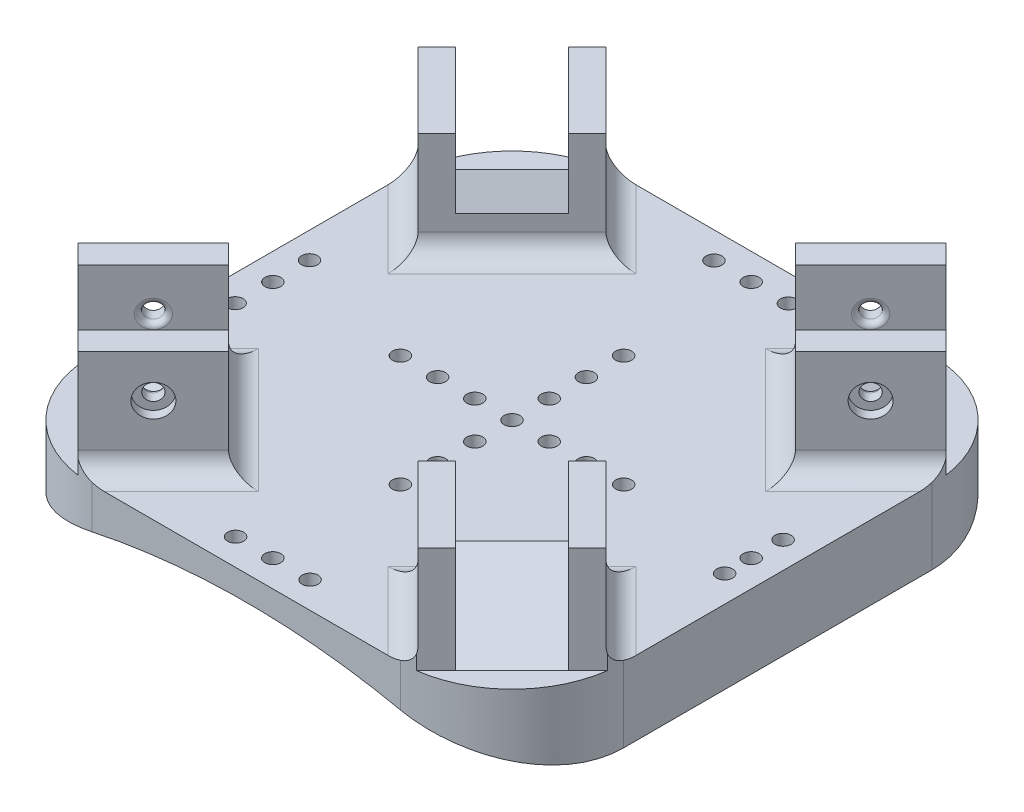
SolidWorks part; units mm, degrees
ref_plane "Front Plane" through (0, 0, 0) normal (0, 0, 1) x (1, 0, 0)
ref_plane "Top Plane" through (0, 0, 0) normal (0, 1, 0) x (1, 0, 0)
ref_plane "Right Plane" through (0, 0, 0) normal (1, 0, 0) x (0, 0, -1)
sketch "Sketch1" plane through (0, 0, 0) normal (0, 0, 1) x (1, 0, 0)
  line L0 (0, 0) -> (50, 0) construction
  line L1 (0, 0) -> (-50, 0) construction
  line L2 (-50, 0) -> (-50, 5) construction
  line L3 (50, 0) -> (50, 5) construction
  line L4 (50, 5) -> (-50, 5) construction
  line L5 (-50, 5) -> (-50, 0)
  line L6 (50, 5) -> (50, 0)
  arc A0 (-50, 0) -> (50, 0) centre (0, -130.767) cw
  arc A1 (50, 5) -> (-50, 5) centre (0, -130.767) ccw
  dimension "D1" = 50
  dimension "D2" = 50
extrude "Boss-Extrude1" add sketch "Sketch1" along normal blind 100
sketch "Sketch2" plane through (0, 0, 100) normal (0, 0, 1) x (1, 0, 0)
  line L0 (0, 13.9143) -> (50, 13.9143) construction
  line L1 (50, 13.9143) -> (50, 5) construction
  line L2 (0, 13.9143) -> (-50, 13.9143) construction
  line L3 (-50, 13.9143) -> (-50, 5) construction
  line L4 (-50, 5) -> (-50, 13.9143)
  line L5 (-50, 13.9143) -> (0, 13.9143)
  line L6 (0, 13.9143) -> (50, 13.9143)
  line L7 (50, 13.9143) -> (50, 5)
  line L8 (50, 5) -> (0, 13.9143)
  line L9 (0, 13.9143) -> (-50, 5)
  arc A0 (50, 5) -> (-50, 5) centre (0, -130.767) ccw construction
  arc M3 (50, 5) -> (-50, 5) centre (0, -130.767) ccw
extrude "Boss-Extrude2" add sketch "Sketch2" against normal blind 100 contours L5 L4 M3 | L7 L6 M3 region at (37.5783, 11.2548, 100) region at (-37.5783, 11.2548, 100)
sketch "Sketch3" plane through (0, 13.9143, 0) normal (0, 1, 0) x (1, 0, 0)
  line L0 (-50, 0) -> (50, -100) construction
  line L1 (50, 0) -> (-50, -100) construction
  circle A0 centre (0, -50) radius 1.5
extrude "Cut-Extrude1" cut sketch "Sketch3" against normal blind 10
sketch "Sketch4" plane through (0, 13.9143, 0) normal (0, 1, 0) x (1, 0, 0)
  line L0 (-50, 0) -> (50, -100) construction
  line L1 (50, 0) -> (-50, -100) construction
  line L2 (31.9688, -0.3536) -> (17.8266, -14.4957)
  line L3 (31.9688, -0.3536) -> (49.6464, -18.0312)
  line L4 (17.8266, -14.4957) -> (35.5043, -32.1734)
  line L5 (49.6464, -18.0312) -> (35.5043, -32.1734)
  line L6 (31.9688, -0.3536) -> (35.5043, -32.1734) construction
  line L7 (17.8266, -14.4957) -> (49.6464, -18.0312) construction
  point P9 (33.7365, -16.2635)
  dimension "D1" = 20
  dimension "D2" = 25
  dimension "D3" = 23
  dimension "D4" = 0
  dimension "D5" = 0
extrude "Boss-Extrude3" add sketch "Sketch4" along normal blind 20
sketch "Sketch5" plane through (33.8388, 0, 33.8388) normal (0.7071, 0, 0.7071) x (0.7071, 0, -0.7071)
  line L0 (2.3553, 20.9143) -> (22.3553, 13.9143)
  line L1 (22.3553, 33.9143) -> (22.3553, 13.9143) construction
  line L2 (2.3553, 33.9143) -> (22.3553, 33.9143)
  line L3 (2.3553, 33.9143) -> (2.3553, 20.9143)
  line L4 (2.3553, 20.9143) -> (22.3553, 20.9143)
  line L5 (22.3553, 33.9143) -> (22.3553, 20.9143)
  line L6 (22.3553, 13.9143) -> (22.3553, 20.9143)
  line M3 (22.3553, 13.9143) -> (22.3553, 33.9143)
  line M4 (22.3553, 33.9143) -> (2.3553, 33.9143)
  line M5 (2.3553, 33.9143) -> (2.3553, 13.9143)
  dimension "D1" = 13
sketch "Sketch6" plane through (33.8388, 0, 33.8388) normal (0.7071, 0, 0.7071) x (0.7071, 0, -0.7071)
  line L0 (2.3553, 33.9143) -> (22.3553, 33.9143) construction
  line L1 (22.3553, 33.9143) -> (22.3553, 13.9143) construction
  circle A0 centre (12.3553, 25.9143) radius 1.55
  dimension "D1" = 8
  dimension "D2" = 10
extrude "Cut-Extrude3" cut sketch "Sketch6" against normal blind 25
extrude "Cut-Extrude4" cut sketch "Sketch5" against normal blind 15 from offset 5 contours L4 M5 M3 M4 | L4 L0 M3 region at (44.9324, 18.581, 22.7453) region at (42.5754, 27.4143, 25.1023) offset against normal yes
sketch "Sketch7" plane through (33.8388, 0, 33.8388) normal (0.7071, 0, 0.7071) x (0.7071, 0, -0.7071)
  circle A0 centre (12.3553, 25.9143) radius 3
extrude "Cut-Extrude5" cut sketch "Sketch7" against normal blind 2
extrude "Cut-Extrude6" cut sketch "Sketch7<2>" along normal blind 2 from offset 25 offset against normal yes
sketch "Sketch7<2>" plane through (33.8388, 0, 33.8388) normal (0.7071, 0, 0.7071) x (0.7071, 0, -0.7071) same geometry as "Sketch7"
fillet "Fillet2" radius 1 2 edges at (40.1359, 25.9143, 20.4707) (29.5293, 25.9143, 9.8641)
fillet "Fillet3" radius 21 4 edges at (50, 6.9572, 0) (-50, 6.9572, 0) (-50, 6.9572, 100) (50, 6.9572, 100)
pattern_circular "CirPattern1" count 4 over 360 about axis through (0, 3.9143, 50) along (0, 1, 0) of "Fillet2", "Cut-Extrude6", "Cut-Extrude5", "Cut-Extrude4", "Cut-Extrude3", "Boss-Extrude3"
fillet "Fillet4" radius 4 12 edges at (42.5754, 13.9143, 25.1023) (24.8977, 13.9143, 7.4246) (-24.8977, 13.9143, 7.4246) (-26.6655, 13.9143, 23.3345) (-42.5754, 13.9143, 25.1023) (-42.5754, 13.9143, 74.8977) (-24.8977, 13.9143, 92.5754) (-26.6655, 13.9143, 76.6655) (42.5754, 13.9143, 74.8977) (26.6655, 13.9143, 76.6655) (24.8977, 13.9143, 92.5754) (26.6655, 13.9143, 23.3345)
sketch "Sketch8" plane through (0, 13.9143, 0) normal (0, 1, 0) x (1, 0, 0)
  line L0 (-50, -23.3345) -> (-50, -76.6655) construction
  line L1 (50, -23.3345) -> (50, -76.6655) construction
  line L2 (-26.6655, -100) -> (26.6655, -100) construction
  line L3 (-26.6655, 0) -> (26.6655, 0) construction
  circle A0 centre (0, -5) radius 1.5
  circle A1 centre (-7, -5) radius 1.5
  circle A2 centre (7, -5) radius 1.5
  circle A3 centre (-45, -50) radius 1.5
  circle A4 centre (-45.0958, -43) radius 1.5
  circle A5 centre (-45.0958, -57) radius 1.5
  circle A6 centre (45, -50) radius 1.5
  circle A7 centre (45, -55) radius 1.5
  circle A8 centre (45, -44) radius 1.5
  circle A9 centre (0, -95) radius 1.5
  circle A10 centre (-7, -95) radius 1.5
  circle A11 centre (7, -95) radius 1.5
  point P28 (0, -100)
  dimension "D1" = 5
  dimension "D2" = 7
  dimension "D3" = 7
  dimension "D4" = 5
  dimension "D5" = 5
  dimension "D6" = 5
  dimension "D7" = 6
  dimension "D8" = 5
  dimension "D9" = 5
  dimension "D10" = 7
  dimension "D11" = 5
  dimension "D12" = 5
  dimension "D13" = 7
  dimension "D14" = 5
  dimension "D15" = 5
  dimension "D16" = 5
  dimension "D17" = 7
  dimension "D18" = 3
  dimension "D19" = 7
  dimension "D20" = 0
extrude "Cut-Extrude7" cut sketch "Sketch8" against normal blind 15
pattern_linear "LPattern2" count 4 spacing 7 along (0, 0, 1) of "Cut-Extrude1"
pattern_linear "LPattern3" count 4 spacing 7 along (0, 0, -1) of "Cut-Extrude1"
pattern_linear "LPattern4" count 4 spacing 7 along (1, 0, 0) of "Cut-Extrude1"
pattern_linear "LPattern5" count 4 spacing 7 along (-1, 0, 0) of "Cut-Extrude1"
